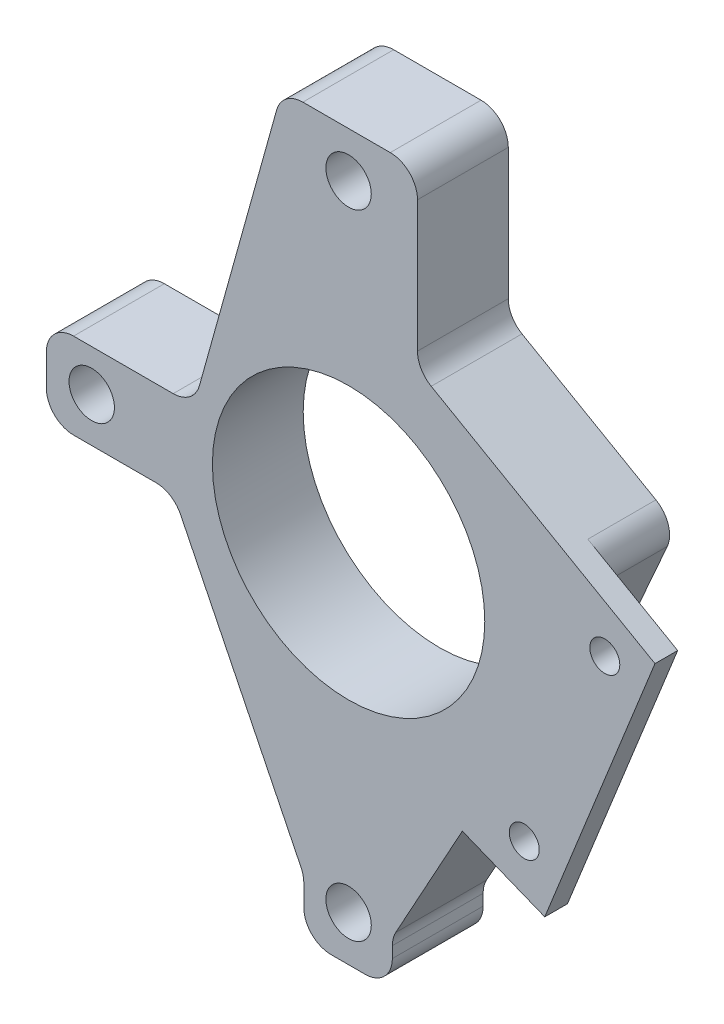
SolidWorks part; units mm, degrees
ref_plane "Front Plane" through (0, 0, 0) normal (0, 0, 1) x (1, 0, 0)
ref_plane "Top Plane" through (0, 0, 0) normal (0, 1, 0) x (1, 0, 0)
ref_plane "Right Plane" through (0, 0, 0) normal (1, 0, 0) x (0, 0, -1)
sketch "Sketch1" plane through (0, 0, 0) normal (0, 0, 1) x (1, 0, 0)
  line L0 (-18.5763, 100.3652) -> (19.2813, 100.3652)
  line L1 (19.2813, 100.3652) -> (19.2813, 51.6625)
  line L2 (19.2813, 51.6625) -> (85.7172, 13.5763)
  line L3 (85.7172, 13.5763) -> (54.8801, -63.2031)
  line L6 (12.2455, -89.5392) -> (12.2455, -102.2392)
  line L7 (12.2455, -102.2392) -> (-12.5308, -102.2392)
  line L8 (-12.5308, -102.2392) -> (-12.5308, -86.8635)
  line L9 (-12.5308, -86.8635) -> (-49.1135, -12.3821)
  line L10 (-49.1135, -12.3821) -> (-84.5631, -12.3821)
  line L11 (-84.5631, -12.3821) -> (-84.5631, 11.5981)
  line L12 (-84.5631, 11.5981) -> (-43.2846, 11.5981)
  line L13 (-43.2846, 11.5981) -> (-18.5763, 100.3652)
  line L14 (54.8801, -63.2031) -> (31.8266, -53.9441)
  line L15 (31.8266, -53.9441) -> (12.2455, -89.5392)
  circle A0 centre (0, 0) radius 38.1
  circle A3 centre (0, 87.6652) radius 6.35
  circle A4 centre (0, -89.5392) radius 6.35
  circle A5 centre (-71.8631, 0) radius 6.35
  dimension "D1" = 76.2
  dimension "D2" = 12.7
  dimension "D3" = 12.7
  dimension "D4" = 12.7
extrude "Boss-Extrude1" add sketch "Sketch1" along normal blind 25.4
sketch "Sketch2" plane through (0, 0, 0) normal (0, 0, 1) x (1, 0, 0)
  line L2 (85.7172, 13.5763) -> (54.8801, -63.2031)
  line L5 (85.7172, 13.5763) -> (66.5382, 24.5712)
  line L6 (85.7172, 13.5763) -> (19.2813, 51.6625) construction
  line L7 (66.5382, 24.5712) -> (31.8266, -53.9441)
  line L8 (54.8801, -63.2031) -> (31.8266, -53.9441)
extrude "Cut-Extrude1" cut sketch "Sketch2" along normal blind 19.05 contours L8 L7 L5 L2
sketch "Sketch3" plane through (0, 0, 25.4) normal (0, 0, 1) x (1, 0, 0)
  circle A0 centre (71.6792, 8.3618) radius 4.191
  circle A1 centre (49.1489, -47.7348) radius 4.191
  dimension "D1" = 8.382
  dimension "D2" = 8.382
  dimension "D3" = 60.452
extrude "Cut-Extrude2" cut sketch "Sketch3" against normal through all
fillet "Fillet1" radius 7.62 12 edges at (-18.5763, 100.3652, 12.7) (19.2813, 100.3652, 12.7) (19.2813, 51.6625, 12.7) (66.5382, 24.5712, 9.525) (12.2455, -89.5392, 12.7) (12.2455, -102.2392, 12.7) (-12.5308, -102.2392, 12.7) (-12.5308, -86.8635, 12.7) (-49.1135, -12.3821, 12.7) (-84.5631, -12.3821, 12.7) (-84.5631, 11.5981, 12.7) (-43.2846, 11.5981, 12.7)
